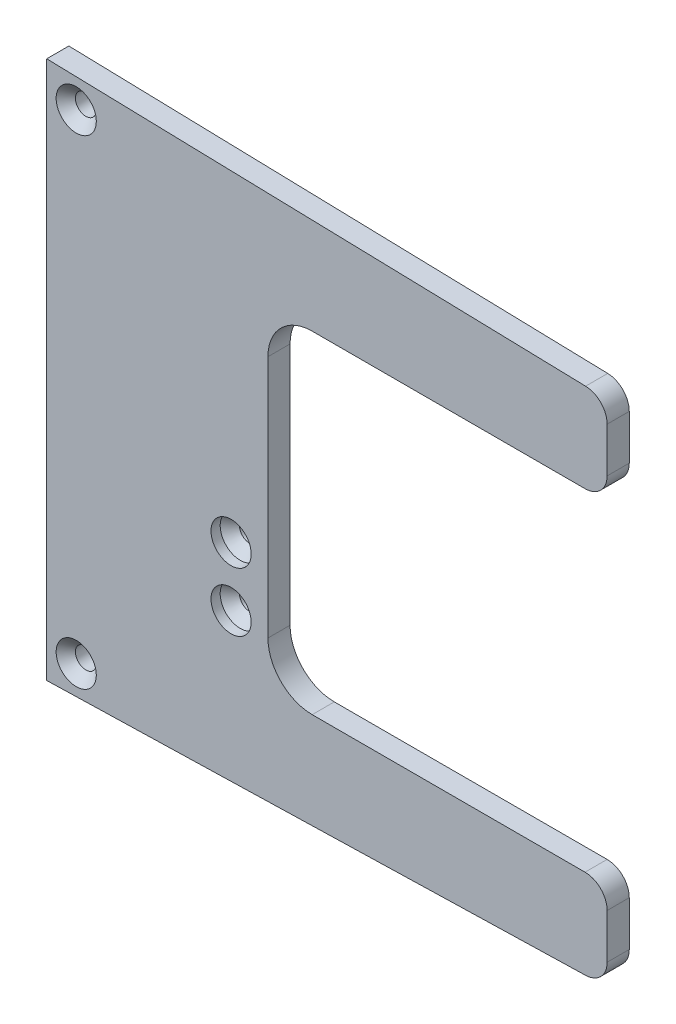
SolidWorks part; units mm, degrees
material "6061-T6 (SS)"
ref_plane "Front Plane" through (0, 0, 0) normal (0, 0, 1) x (1, 0, 0)
ref_plane "Top Plane" through (0, 0, 0) normal (0, 1, 0) x (1, 0, 0)
ref_plane "Right Plane" through (0, 0, 0) normal (1, 0, 0) x (0, 0, -1)
sketch "Length ID" plane through (0, 0, 0) normal (0, 0, 1) x (1, 0, 0)
  line L0 (0, 116.6813) -> (0, -116.6813) construction
  dimension "D1" = 233.3625
sketch "Sketch1" plane through (0, 0, 0) normal (0, 0, 1) x (1, 0, 0)
  line L0 (47.625, 115.9192) -> (-47.625, -115.9192) construction
  line L1 (-47.625, 115.9192) -> (47.625, 115.9192)
  line L2 (-47.625, 115.9192) -> (-47.625, -115.9192)
  line L3 (-47.625, -115.9192) -> (47.625, -115.9192)
  line L4 (47.625, 115.9192) -> (47.625, -115.9192)
  dimension "D1" = 95.25
  dimension "MandrelSideWidth" = 231.8385
extrude "Extrude1" add sketch "Sketch1" along normal blind 9.525
sketch "Cut Length" plane through (0, 0, 0) normal (0, 0, 1) x (1, 0, 0)
  line L0 (-49.2125, 0) -> (49.2125, 0) construction
  line L1 (0, 118.2687) -> (0, -118.2687) construction
  dimension "D1" = 236.5375
  dimension "D2" = 98.425
hole_wizard "CSK for M8 Flat Head Machine Screw1" positions "Sketch3" profile "Sketch2" countersink size "M8" standard "Ansi Metric" end condition through all
sketch "Sketch3" plane through (0, 0, 9.525) normal (0, 0, 1) x (1, 0, 0)
  line L4 (47.625, -115.9192) -> (47.625, 115.9192) construction
  line L5 (31.75, -24.7586) -> (31.75, -50.1586) construction
  line L6 (-47.625, -115.9192) -> (47.625, -115.9192) construction
  point P10 (31.75, -50.1586)
  point P12 (31.75, -24.7586)
  dimension "D4" = 15.875
  dimension "D5" = 25.4
  dimension "MandrelSideHoles" = 65.7606
sketch "Sketch2" plane through (31.75, -50.1586, 9.525) normal (1, 0, 0) x (0, -1, 0)
  line L0 (0, 0) -> (0, 9.525)
  line L1 (0, 9.525) -> (4.5, 9.525)
  line L2 (4.5, 9.525) -> (4.5, 8.1124)
  line L3 (4.5, 8.1124) -> (8.65, 3.9624)
  line L4 (8.65, 3.9624) -> (8.65, 0)
  line L6 (8.65, 0) -> (0, 0)
  line L7 (-4.5, 8.1124) -> (-8.65, 3.9624) construction
  line L11 (0, -6.35) -> (0, 107.95) construction
  dimension "Thru Hole Dia." = 9
  dimension "Thru Hole Depth" = 9.525
  dimension "C'Sink Dia." = 17.3
  dimension "C'Sink Angle" = 90
  dimension "Head Clearance" = 3.9624
hole_wizard "CSK for M8 Flat Head Machine Screw2" positions "Sketch10" profile "Sketch9" countersink size "M8" standard "ANSI Metric" end condition through all
sketch "Sketch10" plane through (0, 0, 9.525) normal (0, 0, 1) x (1, 0, 0)
  line L0 (47.625, 115.9192) -> (-47.625, 115.9192) construction
  line L1 (-47.625, 115.9192) -> (-47.625, -115.9192) construction
  line L2 (-47.625, -115.9192) -> (47.625, -115.9192) construction
  point P0 (-34.925, 103.2192)
  point P1 (-34.925, -103.2192)
  dimension "D1" = 12.7
  dimension "D2" = 12.7
  dimension "D3" = 12.7
sketch "Sketch9" plane through (-34.925, 103.2192, 9.525) normal (1, 0, 0) x (0, -1, 0)
  line L0 (0, 0) -> (0, 9.525)
  line L1 (0, 9.525) -> (4.5, 9.525)
  line L2 (4.5, 9.525) -> (4.5, 4.15)
  line L3 (4.5, 4.15) -> (8.65, 0)
  line L5 (8.65, 0) -> (0, 0)
  line L6 (-4.5, 4.15) -> (-8.65, 0) construction
  line L11 (0, -6.35) -> (0, 107.95) construction
  dimension "Thru Hole Dia." = 9
  dimension "Thru Hole Depth" = 9.525
  dimension "Near C'Sink Dia." = 17.3
  dimension "Near C'Sink Angle" = 90
sketch "Sketch11" plane through (0, 0, 9.525) normal (0, 0, 1) x (1, 0, 0)
  line L0 (-47.625, 115.9192) -> (47.625, 113.425)
  line L1 (47.625, -115.9192) -> (47.625, 115.9192) construction
  line L2 (47.625, 113.425) -> (47.625, 115.9192)
  line L3 (47.625, 115.9192) -> (-47.625, 115.9192)
  line L4 (-47.625, -115.9192) -> (47.625, -115.9192)
  line L5 (47.625, -115.9192) -> (47.625, -113.425)
  line L6 (47.625, -113.425) -> (-47.625, -115.9192)
  dimension "D1" = 1.5
extrude "Cut-Extrude1" cut sketch "Sketch11" against normal up to next
sketch "Sketch12" plane through (0, 0, 9.525) normal (0, 0, 1) x (1, 0, 0)
  line L0 (47.625, 113.425) -> (193.675, 109.6006)
  line L1 (193.675, 109.6006) -> (193.675, 71.5006)
  line L2 (193.675, 71.5006) -> (47.625, 71.5006)
  line L3 (47.625, -113.425) -> (47.625, 113.425) construction
  line L4 (47.625, 71.5006) -> (47.625, 113.425)
  line L5 (47.625, -71.5006) -> (193.675, -71.5006)
  line L6 (193.675, -71.5006) -> (193.675, -109.6006)
  line L7 (193.675, -109.6006) -> (47.625, -113.425)
  line L8 (47.625, -113.425) -> (47.625, -71.5006)
  line L9 (47.625, -113.425) -> (-47.625, -115.9192) construction
  line L10 (-47.625, 115.9192) -> (47.625, 113.425) construction
  line L11 (-47.625, 115.9192) -> (-47.625, -115.9192) construction
  dimension "D1" = 241.3
  dimension "D2" = 38.1
extrude "Boss-Extrude1" add sketch "Sketch12" against normal up to surface (9.525 mm away) up to face at (-30.425, 103.2192, 0)
fillet "Fillet1" radius 9.525 4 edges at (193.675, -109.6006, 4.7625) (193.675, -71.5006, 4.7625) (193.675, 71.5006, 4.7625) (193.675, 109.6006, 4.7625)
fillet "Fillet2" radius 19.05 2 edges at (47.625, -71.5006, 4.7625) (47.625, 71.5006, 4.7625)
equation "\"D1@Cut Length\" = \"D1@Length ID\" + .125"
equation "\"D2@Cut Length\" = \"D1@Sketch1\" + .125"
